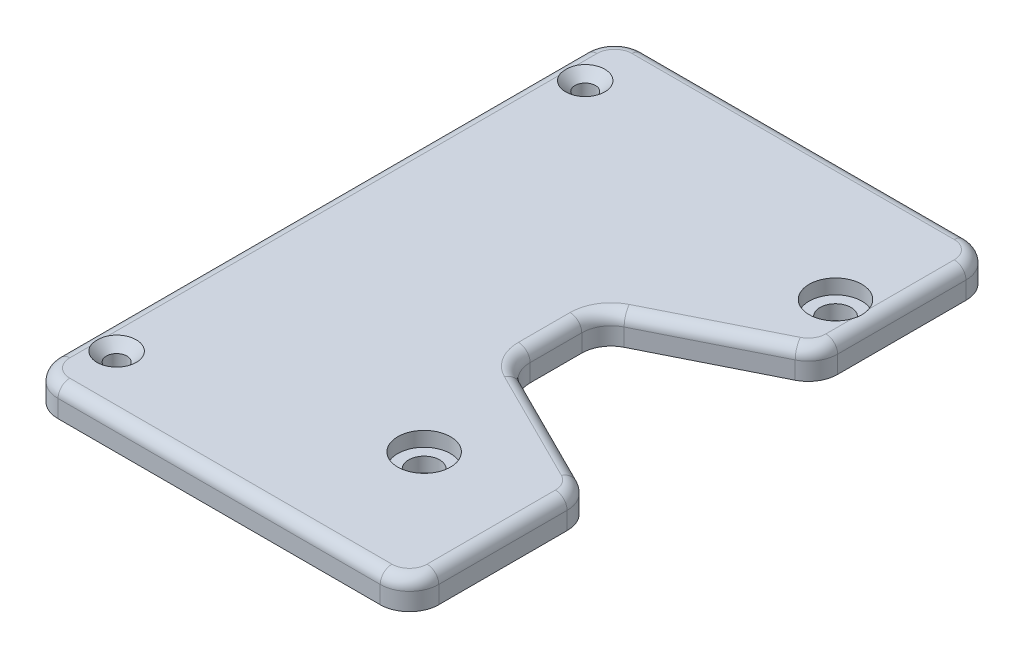
SolidWorks part; units mm, degrees
ref_plane "Front Plane" through (0, 0, 0) normal (0, 0, 1) x (1, 0, 0)
ref_plane "Top Plane" through (0, 0, 0) normal (0, 1, 0) x (1, 0, 0)
ref_plane "Right Plane" through (0, 0, 0) normal (1, 0, 0) x (0, 0, -1)
sketch "Sketch2" plane through (0, 0, 0) normal (0, 1, 0) x (1, 0, 0)
  line L1 (-32.5, 50) -> (32.5, 50)
  line L2 (-32.5, 50) -> (-32.5, -50)
  line L3 (-32.5, -50) -> (32.5, -50)
  line L4 (32.5, 50) -> (32.5, -50)
  line L5 (-32.5, 50) -> (32.5, -50) construction
  line L6 (-32.5, -50) -> (32.5, 50) construction
  circle A0 centre (-27.5, 40) radius 1.75
  circle A1 centre (-27.5, -40) radius 1.75
  circle A2 centre (26.23, 29) radius 2.65
  circle A3 centre (13.65, -28.65) radius 2.65
  point P0 (0, 0)
  dimension "D3" = 3.5
  dimension "D4" = 5
  dimension "D8" = 5.3
  dimension "D9" = 5.3
  dimension "D1" = 65
  dimension "D2" = 100
  dimension "D5" = 5
  dimension "D6" = 10
  dimension "D7" = 10
  dimension "D10" = 18.85
  dimension "D11" = 21.35
  dimension "D12" = 6.27
  dimension "D13" = 21
extrude "Boss-Extrude1" add sketch "Sketch2" along normal blind 5
sketch "Sketch3" plane through (0, 5, 0) normal (0, 1, 0) x (1, 0, 0)
  circle A0 centre (26.23, 29) radius 4.5
  circle A1 centre (13.65, -28.65) radius 4.5
  dimension "D1" = 9
  dimension "D2" = 9
extrude "Cut-Extrude1" cut sketch "Sketch3" against normal blind 2.5
fillet "Fillet1" radius 5 4 edges at (32.5, 2.5, 50) (-32.5, 2.5, -50) (32.5, 2.5, -50) (-32.5, 2.5, 50)
chamfer "Chamfer1" distance 1.6 angle 45 2 edges at (-27.5, 5, 41.75) (-27.5, 5, -38.25)
sketch "Sketch4" plane through (0, 5, 0) normal (0, 1, 0) x (1, 0, 0)
  line L5 (7.5, 7.5) -> (7.5, -7.5)
  line L6 (7.5, -7.5) -> (32.5, -20)
  line L7 (32.5, -45) -> (32.5, 45) construction
  line L8 (32.5, -20) -> (32.5, 20)
  line L9 (32.5, 20) -> (7.5, 7.5)
  point P6 (7.5, 0)
  point P7 (32.5, 0)
  dimension "D1" = 40
  dimension "D2" = 25
  dimension "D3" = 15
extrude "Cut-Extrude2" cut sketch "Sketch4" against normal through all
fillet "Fillet3" radius 5 4 edges at (32.5, 2.5, -20) (32.5, 2.5, 20) (7.5, 2.5, 7.5) (7.5, 2.5, -7.5)
fillet "Fillet2" radius 2 16 edges at (-31.0355, 5, 48.5355) (-32.5, 5, 0) (-31.0355, 5, -48.5355) (0, 5, -50) (31.0355, 5, -48.5355) (32.5, 5, -34.0451) (32.5, 5, 34.0451) (31.0355, 5, 48.5355) (0, 5, 50) (7.5, 5, 0) (31.7533, 5, -20.4615) (20, 5, -13.75) (8.2467, 5, -7.0385) (8.2467, 5, 7.0385) (20, 5, 13.75) (31.7533, 5, 20.4615)
